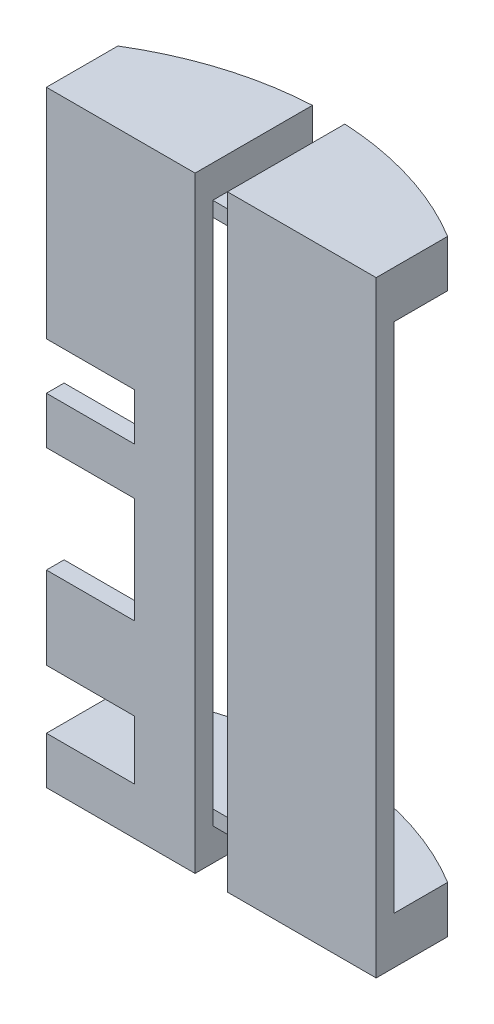
SolidWorks part; units mm, degrees
ref_plane "Front Plane" through (0, 0, 0) normal (0, 0, 1) x (1, 0, 0)
ref_plane "Top Plane" through (0, 0, 0) normal (0, 1, 0) x (1, 0, 0)
ref_plane "Right Plane" through (0, 0, 0) normal (1, 0, 0) x (0, 0, -1)
sketch "Sketch2" plane through (0, 0, 0) normal (0, 1, 0) x (1, 0, 0)
  circle A0 centre (0, 0) radius 53.75
  dimension "D1" = 107.5
extrude "Boss-Extrude1" add sketch "Sketch2" along normal blind 103
sketch "Sketch3" plane through (0, 103, 0) normal (0, 1, 0) x (1, 0, 0)
  line L3 (53.75, 33.75) -> (53.75, -53.75)
  line L4 (53.75, -53.75) -> (-53.75, -53.75)
  line L5 (-53.75, -53.75) -> (-53.75, 33.75)
  line L8 (0, 0) -> (0, 53.75) construction
  line L9 (-53.75, 33.75) -> (53.75, 33.75)
  circle A0 centre (0, 0) radius 53.75 construction
  dimension "D1" = 20
extrude "Cut-Extrude2" cut sketch "Sketch3" against normal through all both and the other way through all
ref_plane "Plane1" through (0, 0, -53.75) normal (0, 0, 1) x (1, 0, 0)
sketch "Sketch6" plane through (0, 0, -53.75) normal (0, 0, 1) x (1, 0, 0)
  line L0 (-41.833, 0) -> (-41.833, 103) construction
  line L1 (-41.833, 95) -> (41.833, 95)
  line L2 (-41.833, 95) -> (-41.833, 8)
  line L3 (-41.833, 8) -> (41.833, 8)
  line L4 (41.833, 95) -> (41.833, 8)
  line L5 (41.833, 103) -> (41.833, 0) construction
  point P8 (41.833, 51.5)
  point P9 (41.833, 51.5)
  dimension "D1" = 87
extrude "Cut-Extrude6" cut sketch "Sketch6" along normal blind 17
sketch "Sketch7" plane through (0, 0, 0) normal (0, -1, 0) x (1, 0, 0)
  line L0 (2.75, -33.75) -> (2.75, -36.75)
  line L1 (41.833, -33.75) -> (-41.833, -33.75) construction
  line L2 (2.75, -36.75) -> (-2.75, -36.75)
  line L3 (-2.75, -36.75) -> (-2.75, -33.75)
  line L4 (-2.75, -33.75) -> (2.75, -33.75)
  point P4 (0, -33.75)
  point P7 (0, -33.75)
  dimension "D1" = 5.5
  dimension "D2" = 3
extrude "Cut-Extrude7" cut sketch "Sketch7" against normal through all both and the other way through all
sketch "Sketch8" plane through (0, 0, -33.75) normal (0, 0, 1) x (1, 0, 0)
  line L0 (2.75, 103) -> (2.75, 95) construction
  line L1 (-2.75, 103) -> (2.75, 103)
  line L2 (-2.75, 103) -> (-2.75, 97.5)
  line L3 (-2.75, 97.5) -> (2.75, 97.5)
  line L4 (2.75, 103) -> (2.75, 97.5)
  line L5 (2.75, 8) -> (2.75, 0) construction
  line L6 (-2.75, 0) -> (2.75, 0)
  line L7 (-2.75, 0) -> (-2.75, 5.5)
  line L8 (-2.75, 5.5) -> (2.75, 5.5)
  line L9 (2.75, 0) -> (2.75, 5.5)
  dimension "D1" = 5.5
  dimension "D2" = 5.5
extrude "Cut-Extrude8" cut sketch "Sketch8" against normal through all both and the other way through all
sketch "Sketch10" plane through (0, 0, -53.75) normal (0, 0, 1) x (1, 0, 0)
  line L0 (39.2237, 95) -> (2.75, 95) construction
  line L1 (28, 95) -> (-28, 95) construction
  line L2 (28, 95) -> (28, 8) construction
  line L3 (28, 8) -> (-28, 8) construction
  line L4 (-28, 95) -> (-28, 8) construction
  line L5 (39.2237, 8) -> (-39.2237, 8) construction
  line L16 (2.75, 0) -> (41.833, 0) construction
  line L17 (41.833, 103) -> (28, 103)
  line L18 (41.833, 103) -> (41.833, 0)
  line L19 (41.833, 0) -> (28, 0)
  line L20 (28, 103) -> (28, 0)
  line L21 (-2.75, 103) -> (-41.833, 103) construction
  line L22 (-28, 103) -> (-41.833, 103)
  line L23 (-28, 103) -> (-28, 0)
  line L24 (-28, 0) -> (-41.833, 0)
  line L25 (-41.833, 103) -> (-41.833, 0)
  point P8 (0, 8)
  dimension "D1" = 56
extrude "Cut-Extrude11" cut sketch "Sketch10" against normal blind 42 and the other way through all
sketch "Sketch11" plane through (0, 0, -36.75) normal (0, 0, -1) x (-1, 0, 0)
  line L1 (28, 8) -> (13, 8)
  line L2 (28, 8) -> (28, 18)
  line L3 (28, 18) -> (13, 18)
  line L4 (13, 8) -> (13, 18)
  line L5 (28, 32) -> (13, 32)
  line L6 (28, 32) -> (28, 50)
  line L7 (28, 50) -> (13, 50)
  line L8 (13, 32) -> (13, 50)
  line L9 (28, 8) -> (-28, 8) construction
  line L10 (28, 58) -> (13, 58)
  line L11 (28, 58) -> (28, 66)
  line L12 (28, 66) -> (13, 66)
  line L13 (13, 58) -> (13, 66)
  line L14 (28, 95) -> (28, 8) construction
  line L15 (28, 8) -> (2.75, 8) construction
  dimension "D1" = 15
  dimension "D2" = 10
  dimension "D3" = 15
  dimension "D4" = 42
  dimension "D5" = 24
  dimension "D6" = 15
  dimension "D7" = 58
  dimension "D8" = 50
extrude "Cut-Extrude12" cut sketch "Sketch11" against normal through all both and the other way through all
